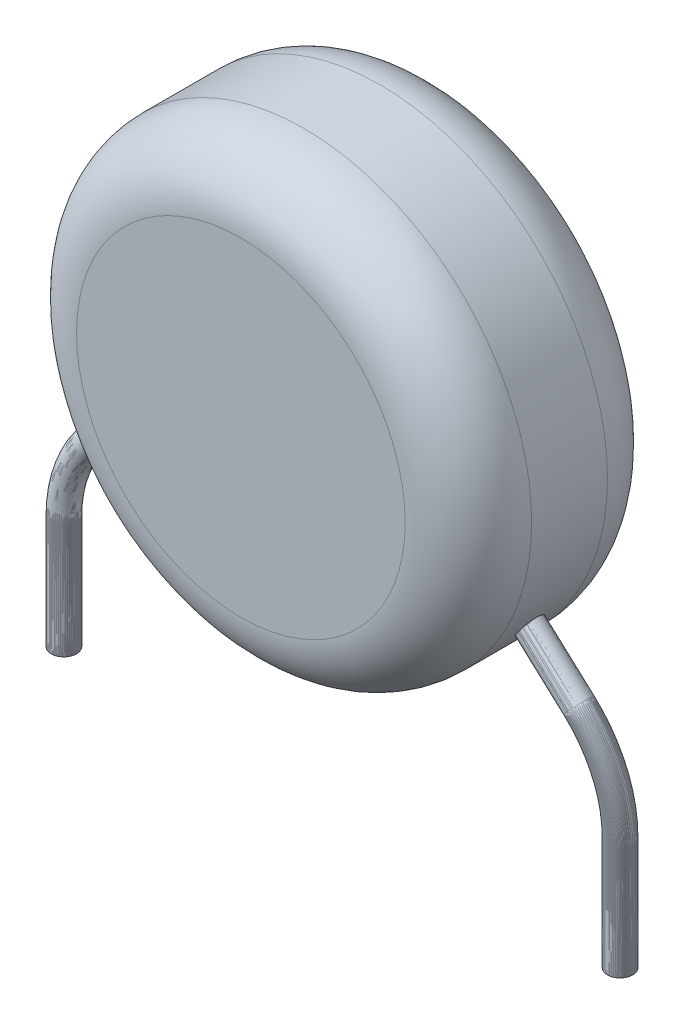
SolidWorks part; units mm, degrees
ref_plane "Спереди" through (0, 0, 0) normal (0, 0, 1) x (1, 0, 0)
ref_plane "Сверху" through (0, 0, 0) normal (0, 1, 0) x (1, 0, 0)
ref_plane "Справа" through (0, 0, 0) normal (1, 0, 0) x (0, 0, -1)
sketch "Эскиз1" plane through (0, 0, 0) normal (0, 0, 1) x (1, 0, 0)
  line L0 (0, 0) -> (0, 51.7005) construction
  circle A0 centre (0, 15) radius 9
  dimension "D1" = 18
  dimension "D2" = 15
extrude "Вытянуть1" add sketch "Эскиз1" along normal blind 4 and the other way blind 4
sketch "Эскиз2" plane through (0, 0, 0) normal (0, 0, 1) x (1, 0, 0)
  line L0 (0, 0) -> (-20.5141, 0) construction
  line L1 (0, 0) -> (0, 20.3292) construction
  line L2 (-11, 0) -> (-11, 4.4836)
  line L3 (-9.3677, 8.1794) -> (-3.4984, 13.5278)
  line L4 (-0.1306, 14.832) -> (0.1306, 14.832)
  line L5 (3.4984, 13.5278) -> (9.3677, 8.1794)
  line L6 (11, 4.4836) -> (11, 0)
  arc A0 (-11, 4.4836) -> (-9.3677, 8.1794) centre (-6, 4.4836) cw
  arc A1 (9.3677, 8.1794) -> (11, 4.4836) centre (6, 4.4836) cw
  arc A2 (-3.4984, 13.5278) -> (-0.1306, 14.832) centre (-0.1306, 9.832) cw
  arc A3 (0.1306, 14.832) -> (3.4984, 13.5278) centre (0.1306, 9.832) cw
  dimension "D2" = 5
  dimension "D1" = 22
sketch "Эскиз3" plane through (0, 0, 0) normal (0, 1, 0) x (1, 0, 0)
  line L0 (-9.3677, 0) -> (-3.4984, 0) construction
  line L1 (0, 0) -> (-20.5141, 0) construction
  line L2 (9.3677, 0) -> (11, 0) construction
  circle A0 centre (-11, 0) radius 0.5
  circle A1 centre (11, 0) radius 0.5
  dimension "D1" = 1
extrude "Вытянуть2" add sketch "Эскиз3" along normal blind 4.48
surface "Поверхность-По траектории2"
sketch "Эскиз3<4>" plane through (0, 0, 0) normal (0, 1, 0) x (1, 0, 0) same geometry as "Эскиз3"
fillet "Скругление1" radius 2.5 2 edges at (9, 15, -4) (9, 15, 4)
